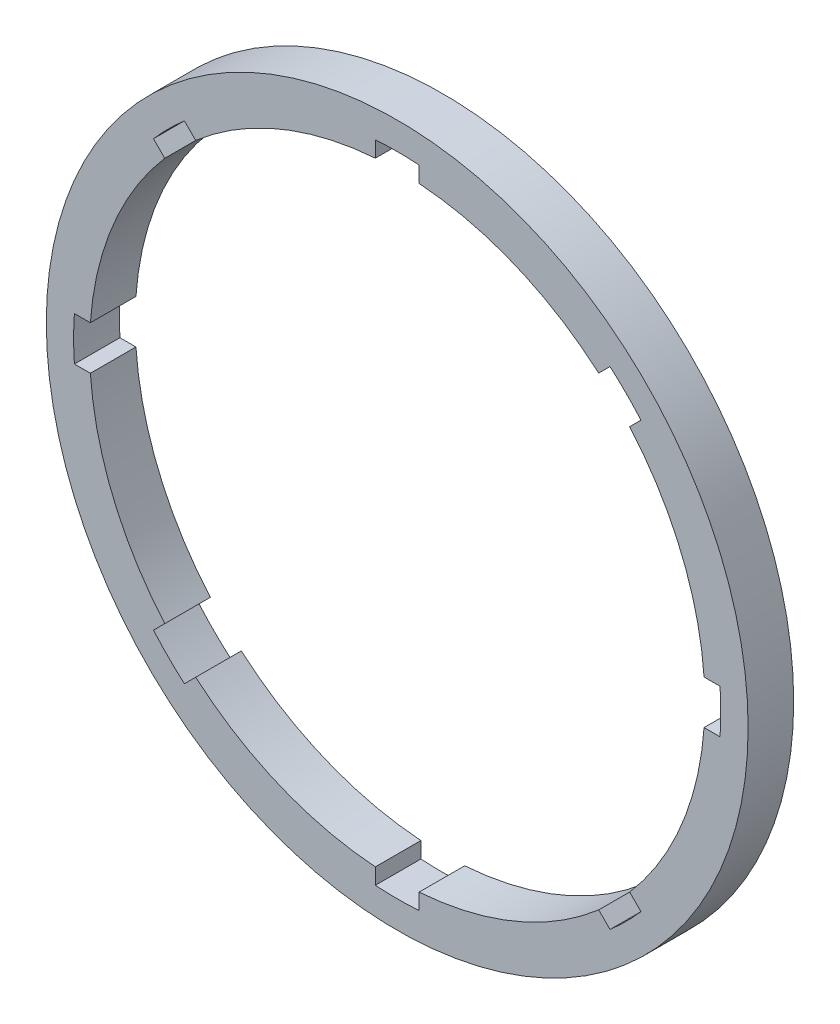
SolidWorks part; units mm, degrees
ref_plane "Alzado" through (0, 0, 0) normal (0, 0, 1) x (1, 0, 0)
ref_plane "Planta" through (0, 0, 0) normal (0, 1, 0) x (1, 0, 0)
ref_plane "Vista lateral" through (0, 0, 0) normal (1, 0, 0) x (0, 0, -1)
sketch "Croquis1" plane through (0, 0, 0) normal (0, 0, 1) x (1, 0, 0)
  line L0 (-38.5, 0) -> (38.5, 0) construction
  line L1 (0, 38.5) -> (0, -38.5) construction
  line L2 (0, 0) -> (-27.2236, 27.2236) construction
  line L3 (0, 0) -> (26.6453, -26.6453) construction
  line L4 (27.2236, 27.2236) -> (0, 0) construction
  line L5 (0, 0) -> (-27.2236, -27.2236) construction
  line L6 (-2.4, 33.6646) -> (-2.4, 35.4188)
  line L7 (2.4, 33.6646) -> (2.4, 35.4188)
  line L8 (2.4, -33.6646) -> (2.4, -35.4188)
  line L9 (-2.4, -33.6646) -> (-2.4, -35.4188)
  line L10 (-35.4188, 2.4) -> (-33.6646, 2.4)
  line L11 (-35.4188, -2.4) -> (-33.6646, -2.4)
  line L12 (35.4188, -2.4) -> (33.6646, -2.4)
  line L13 (35.4188, 2.4) -> (33.6646, 2.4)
  line L14 (-23.3478, 26.7419) -> (-22.1074, 25.5015)
  line L15 (-26.7419, 23.3478) -> (-25.5015, 22.1074)
  line L16 (26.7419, -23.3478) -> (25.5015, -22.1074)
  line L17 (23.3478, -26.7419) -> (22.1074, -25.5015)
  line L18 (22.1074, 25.5015) -> (23.3478, 26.7419)
  line L19 (25.5015, 22.1074) -> (26.7419, 23.3478)
  line L20 (-22.1074, -25.5015) -> (-23.3478, -26.7419)
  line L21 (-25.5015, -22.1074) -> (-26.7419, -23.3478)
  circle A0 centre (0, 0) radius 38.5
  arc A1 (-23.3478, 26.7419) -> (-26.7419, 23.3478) centre (0, 0) ccw
  arc A2 (-2.4, 33.6646) -> (-22.1074, 25.5015) centre (0, 0) ccw
  arc A3 (2.4, 35.4188) -> (-2.4, 35.4188) centre (0, 0) ccw
  arc A4 (-25.5015, 22.1074) -> (-33.6646, 2.4) centre (0, 0) ccw
  arc A5 (22.1074, 25.5015) -> (2.4, 33.6646) centre (0, 0) ccw
  arc A6 (26.7419, 23.3478) -> (23.3478, 26.7419) centre (0, 0) ccw
  arc A7 (33.6646, 2.4) -> (25.5015, 22.1074) centre (0, 0) ccw
  arc A8 (35.4188, -2.4) -> (35.4188, 2.4) centre (0, 0) ccw
  arc A9 (25.5015, -22.1074) -> (33.6646, -2.4) centre (0, 0) ccw
  arc A10 (23.3478, -26.7419) -> (26.7419, -23.3478) centre (0, 0) ccw
  arc A11 (2.4, -33.6646) -> (22.1074, -25.5015) centre (0, 0) ccw
  arc A12 (-2.4, -35.4188) -> (2.4, -35.4188) centre (0, 0) ccw
  arc A13 (-22.1074, -25.5015) -> (-2.4, -33.6646) centre (0, 0) ccw
  arc A14 (-26.7419, -23.3478) -> (-23.3478, -26.7419) centre (0, 0) ccw
  arc A15 (-33.6646, -2.4) -> (-25.5015, -22.1074) centre (0, 0) ccw
  arc A16 (-35.4188, 2.4) -> (-35.4188, -2.4) centre (0, 0) ccw
  dimension "D1" = 77
  dimension "D2" = 71
  dimension "D6" = 67.5
  dimension "D3" = 45
  dimension "D4" = 45
  dimension "D5" = 45
  dimension "D7" = 2.4
  dimension "D8" = 2.4
  dimension "D9" = 2.4
  dimension "D10" = 2.4
  dimension "D11" = 2.4
  dimension "D12" = 2.4
  dimension "D13" = 2.4
  dimension "D14" = 2.4
extrude "Saliente-Extruir4" add sketch "Croquis1" along normal blind 5 contours A0 | L14 A2 L6 A3 L7 A5 L18 A6 L19 A7 L13 A8 L12 A9 L16 A10 L17 A11 L8 A12 L9 A13 L20 A14 L21 A15 L11 A16 L10 A4 L15 A1
